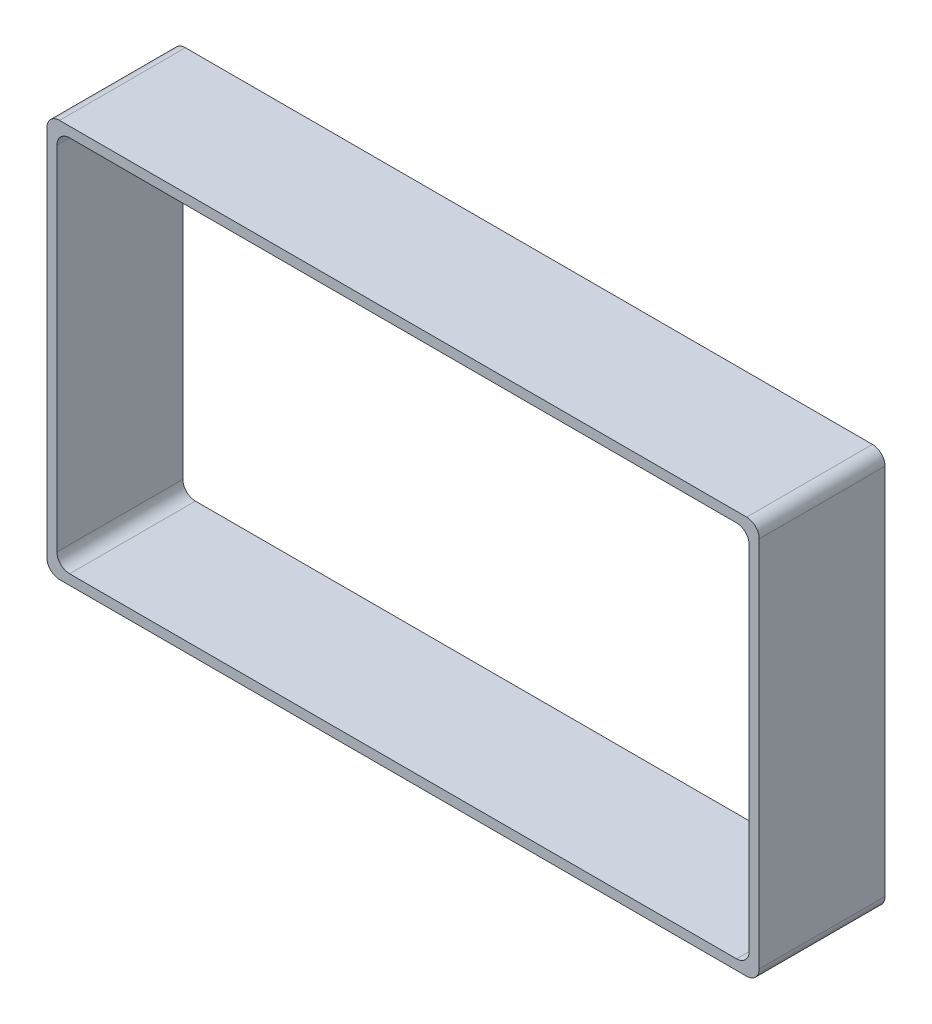
SolidWorks part; units mm, degrees
ref_plane "Plan de face" through (0, 0, 0) normal (0, 0, 1) x (1, 0, 0)
ref_plane "Plan de dessus" through (0, 0, 0) normal (0, 1, 0) x (1, 0, 0)
ref_plane "Plan de droite" through (0, 0, 0) normal (1, 0, 0) x (0, 0, -1)
sketch "Esquisse1" plane through (0, 0, 0) normal (0, 0, 1) x (1, 0, 0)
  line L0 (-28.3, 15.8) -> (28.3, 15.8)
  line L1 (-27.5, 15) -> (27.5, 15)
  line L2 (-27.5, 15) -> (-27.5, -15)
  line L3 (-27.5, -15) -> (27.5, -15)
  line L4 (27.5, 15) -> (27.5, -15)
  line L5 (-27.5, 15) -> (27.5, -15) construction
  line L6 (-27.5, -15) -> (27.5, 15) construction
  line L7 (28.3, 15.8) -> (28.3, -15.8)
  line L8 (-28.3, -15.8) -> (28.3, -15.8)
  line L9 (-28.3, 15.8) -> (-28.3, -15.8)
  point P0 (0, 0)
  dimension "D1" = 30
  dimension "D2" = 55
  dimension "D3" = 0.8
extrude "Boss.-Extru.1" add sketch "Esquisse1" along normal blind 10
fillet "Congé1" radius 1 8 edges at (-27.5, 15, 5) (-27.5, -15, 5) (27.5, -15, 5) (27.5, 15, 5) (28.3, -15.8, 5) (-28.3, -15.8, 5) (-28.3, 15.8, 5) (28.3, 15.8, 5)
